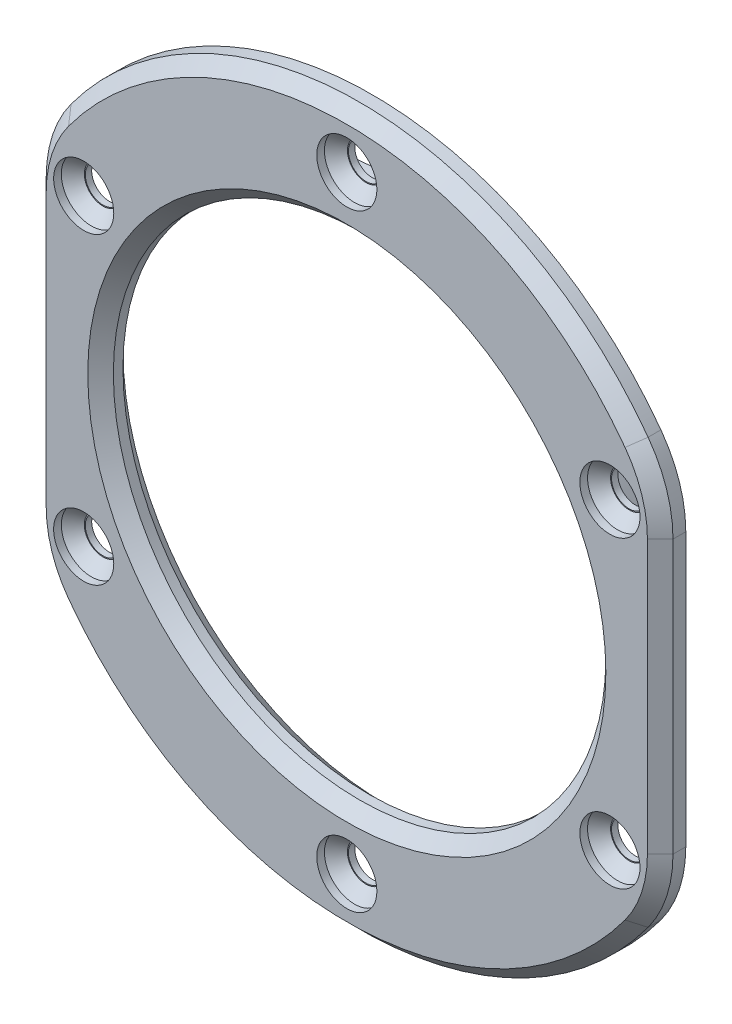
SolidWorks part; units mm, degrees
ref_plane "Front Plane" through (0, 0, 0) normal (0, 0, 1) x (1, 0, 0)
ref_plane "Top Plane" through (0, 0, 0) normal (0, 1, 0) x (1, 0, 0)
ref_plane "Right Plane" through (0, 0, 0) normal (1, 0, 0) x (0, 0, -1)
sketch "Sketch1" plane through (0, 0, 0) normal (0, 0, 1) x (1, 0, 0)
  circle A0 centre (0, 0) radius 19.25
  circle A1 centre (0, 0) radius 28
  dimension "D1" = 38.5
  dimension "D2" = 56
extrude "Boss-Extrude1" add sketch "Sketch1" along normal blind 2
sketch "Sketch2" plane through (0, 0, 0) normal (0, 0, -1) x (-1, 0, 0)
  circle A0 centre (0, 0) radius 19.25
  circle A1 centre (0, 0) radius 22.15
  circle A2 centre (0, 0) radius 19.25 construction
  dimension "D1" = 44.3
extrude "Boss-Extrude2" add sketch "Sketch2" along normal blind 1
sketch "Sketch3" plane through (0, 0, 2) normal (0, 0, 1) x (1, 0, 0)
  circle A0 centre (0, 23.75) radius 1.375
  circle A1 centre (20.5681, 11.875) radius 1.375
  circle A2 centre (20.5681, -11.875) radius 1.375
  circle A3 centre (0, -23.75) radius 1.375
  circle A4 centre (-20.5681, -11.875) radius 1.375
  circle A5 centre (-20.5681, 11.875) radius 1.375
  circle A6 centre (0, 0) radius 23.75 construction
  point P14 (0, 0)
  dimension "D2" = 2.75
  dimension "D3" = 47.5
  dimension "D1" = 6
extrude "Cut-Extrude1" cut sketch "Sketch3" against normal through all
sketch "Sketch4" plane through (0, 0, 2) normal (0, 0, 1) x (1, 0, 0)
  line L0 (0, 37.6944) -> (0, -37.3588) construction
  line L1 (24.5, 26.7836) -> (24.5, -27.4399)
  line L2 (-37.3946, 26.7836) -> (-24.5, 26.7836)
  line L3 (-37.3946, 26.7836) -> (-37.3946, -27.4399)
  line L4 (-37.3946, -27.4399) -> (-24.5, -27.4399)
  line L5 (-24.5, 26.7836) -> (-24.5, -27.4399)
  line L6 (37.3946, -27.4399) -> (24.5, -27.4399)
  line L7 (37.3946, 26.7836) -> (37.3946, -27.4399)
  line L8 (37.3946, 26.7836) -> (24.5, 26.7836)
  dimension "D1" = 49
extrude "Cut-Extrude2" cut sketch "Sketch4" against normal through all
fillet "Fillet1" radius 10 4 edges at (24.5, 13.5554, 1) (24.5, -13.5554, 1) (-24.5, -13.5554, 1) (-24.5, 13.5554, 1)
sketch "Sketch5" plane through (0, 0, 2) normal (0, 0, 1) x (1, 0, 0)
  circle A0 centre (0, 23.75) radius 2.35
  circle A1 centre (20.5681, 11.875) radius 2.35
  circle A2 centre (-20.5681, 11.875) radius 2.35
  circle A3 centre (20.5681, -11.875) radius 2.35
  circle A4 centre (0, -23.75) radius 2.35
  circle A5 centre (-20.5681, -11.875) radius 2.35
  dimension "D1" = 4.7
extrude "Cut-Extrude3" cut sketch "Sketch5" against normal blind 1.5
chamfer "Chamfer2" distance 0.9 angle 45 6 edges at (-18.2181, -11.875, 0.5) (2.35, -23.75, 0.5) (22.9181, -11.875, 0.5) (22.9181, 11.875, 0.5) (2.35, 23.75, 0.5) (-18.2181, 11.875, 0.5)
chamfer "Chamfer1" distance 1 angle 45 9 edges at (0, -28, 2) (24.0015, -13.7834, 2) (-24.0015, -13.7834, 2) (24.5, 0, 2) (-24.5, 0, 2) (24.0015, 13.7834, 2) (-24.0015, 13.7834, 2) (0, 28, 2) (19.25, 0, 2)
chamfer "Chamfer3" distance 1.25 angle 45 1 edges at (-19.25, 0, -1)
